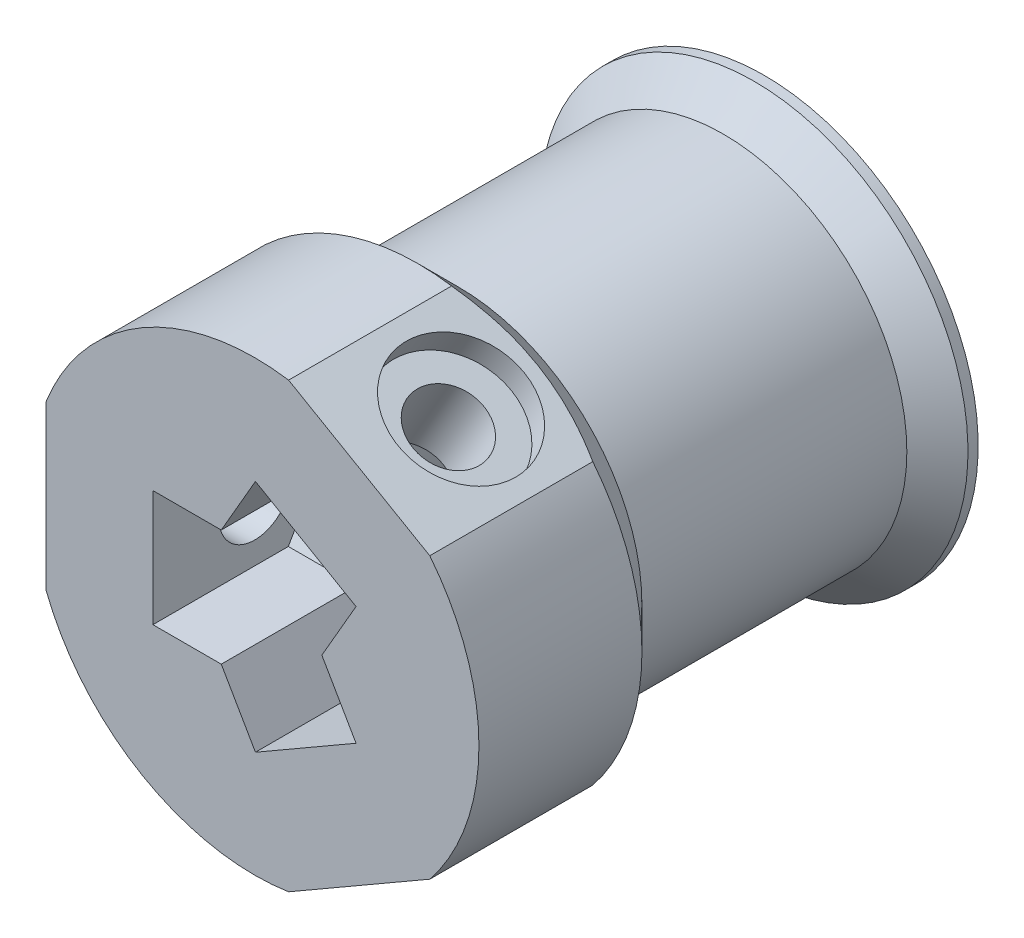
SolidWorks part; units mm, degrees
ref_plane "Front" through (0, 0, 0) normal (0, 0, 1) x (1, 0, 0)
ref_plane "Top" through (0, 0, 0) normal (0, 1, 0) x (1, 0, 0)
ref_plane "Right" through (0, 0, 0) normal (1, 0, 0) x (0, 0, -1)
sketch "Sketch1" plane through (0, 0, 0) normal (0, 0, 1) x (1, 0, 0)
  circle A0 centre (0, 0) radius 11
  dimension "D1" = 22
extrude "Boss-Base Flange" add sketch "Sketch1" along normal blind 2 draft 45
sketch "Sketch2" plane through (0, 0, 2) normal (0, 0, 1) x (1, 0, 0)
  circle A0 centre (0, 0) radius 9 construction
  circle A1 centre (0, 0) radius 9
extrude "Boss-Spectra Spool" add sketch "Sketch2" along normal blind 13
sketch "Sketch3" plane through (0, 0, 15) normal (0, 0, 1) x (1, 0, 0)
  circle A0 centre (0, 0) radius 9 construction
  circle A1 centre (0, 0) radius 9
extrude "Boss-Top Flange" add sketch "Sketch3" along normal blind 2 draft 45 draft outward yes
sketch "Sketch4" plane through (0, 0, 17) normal (0, 0, 1) x (1, 0, 0)
  line L0 (-11, 9.8044) -> (-11, -8.8054) construction
  circle A0 centre (0, 0) radius 11 construction
  circle A1 centre (0, 0) radius 11
extrude "Boss-Top Extension" add sketch "Sketch4" along normal blind 8
sketch "Sketch5" plane through (0, 0, 0) normal (0, 0, -1) x (-1, 0, 0)
  circle A0 centre (0, 0) radius 2.6
  dimension "D1" = 5.2
extrude "Cut-Stepper Shaft" cut sketch "Sketch5" against normal through all
ref_plane "Plane1" through (-11, 0, 0) normal (1, 0, 0) x (0, 0, -1)
sketch "Sketch7" plane through (-11, 0, 0) normal (1, 0, 0) x (0, 0, -1)
  line L0 (-17, 11) -> (-17, -11) construction
  circle A0 centre (-20, 0) radius 1.75
  dimension "D1" = 3.5
  dimension "D2" = 3
extrude "Cut-Set Screw Hole" cut sketch "Sketch7" along normal up to surface (11 mm away) up to plane "Right"
sketch "Sketch8" plane through (-11, 0, 0) normal (1, 0, 0) x (0, 0, -1)
  circle A0 centre (-20, 0) radius 3.1
  dimension "D1" = 6.2
extrude "Cut-Screw Head Slot" cut sketch "Sketch8" along normal blind 2
sketch "Sketch6" plane through (0, 0, 25) normal (0, 0, 1) x (1, 0, 0)
  line L1 (-10.247, 4) -> (-11, 4)
  line L2 (-10.247, 4) -> (-10.247, -4)
  line L3 (-10.247, -4) -> (-11, -4)
  line L4 (-11, 4) -> (-11, -4)
  circle A0 centre (0, 0) radius 11 construction
  dimension "D1" = 8
extrude "Cut-Flaten" cut sketch "Sketch6" against normal up to surface (8 mm away) up to face at (9, 0, 15)
sketch "Sketch10" plane through (0, 0, 0) normal (-1, 0, 0) x (0, 0, 1)
  line L1 (23.2909, 0) -> (21.6454, 2.85)
  line L2 (21.6454, 2.85) -> (18.3546, 2.85)
  line L3 (18.3546, 2.85) -> (16.7091, 0)
  line L4 (16.7091, 0) -> (18.3546, -2.85)
  line L5 (18.3546, -2.85) -> (21.6454, -2.85)
  line L6 (21.6454, -2.85) -> (23.2909, 0)
  circle A0 centre (20, 0) radius 2.85 construction
  dimension "D1" = 5.7
extrude "Cut-Nut Hole" cut sketch "Sketch10" along normal blind 5
sketch "Sketch11" plane through (0, 0, 0) normal (-1, 0, 0) x (0, 0, 1)
  line L0 (25, -11) -> (25, 11) construction
  line L1 (25, 2.85) -> (21.6454, 2.85)
  line L2 (25, 2.85) -> (25, -2.85)
  line L3 (25, -2.85) -> (21.6454, -2.85)
  line L4 (21.6454, 2.85) -> (21.6454, -2.85)
extrude "Cut-Nut Slot" cut sketch "Sketch11" along normal up to surface (5 mm away) up to face at (-5, 0, 21.75)
ref_axis "Axis1" through (0, 0, -80.9) along (0, 0, 1)
pattern_circular "CirPattern1" count 3 over 360 about axis through (0, 0, -80.9) along (0, 0, 1) of "Cut-Set Screw Hole", "Cut-Screw Head Slot", "Cut-Flaten", "Cut-Nut Hole", "Cut-Nut Slot"
sketch "Sketch13" plane through (0, 0, 25) normal (0, 0, 1) x (1, 0, 0)
  line L0 (-2.6, 0) -> (-5, 0) construction
  line L1 (-4.066, 1) -> (-4.9321, 0.5)
  line L2 (-4.9321, 0.5) -> (-4.9321, -0.5)
  line L3 (-4.9321, -0.5) -> (-4.066, -1)
  line L4 (-4.066, -1) -> (-3.2, -0.5)
  line L5 (-3.2, -0.5) -> (-3.2, 0.5)
  line L6 (-3.2, 0.5) -> (-4.066, 1)
  line L8 (-2.6, 2.85) -> (-2.6, -2.85) construction
  line L9 (-1.6454, 2.85) -> (-5, 2.85) construction
  line L10 (-1.6454, -2.85) -> (-5, -2.85) construction
  circle A0 centre (-4.066, 0) radius 0.866 construction
  arc A1 (-2.6, 0) -> (-1.3, -2.2517) centre (0, 0) ccw construction
  dimension "D1" = 2
  dimension "D2" = 0.6
extrude "Cut-Thread Hole" cut sketch "Sketch13" against normal through all
sketch "Sketch14" plane through (0, 0, 0) normal (0, 0, 1) x (1, 0, 0)
  line L0 (-11, 9.2906) -> (-11, -9.0052) construction
  circle A0 centre (0, 0) radius 11 construction
ref_plane "Plane2" through (-5.5, 0, 5.5) normal (-0.7071, 0, 0.7071) x (0.7071, 0, 0.7071)
sketch "Sketch15" plane through (-5.5, 0, 5.5) normal (-0.7071, 0, 0.7071) x (0.7071, 0, 0.7071)
  line L1 (-4.9399, 0.5) -> (-3.4399, 0.5)
  line L2 (-4.9399, 0.5) -> (-4.9399, -0.5)
  line L3 (-4.9399, -0.5) -> (-3.4399, -0.5)
  line L4 (-3.4399, 0.5) -> (-3.4399, -0.5)
  ellipse E0 centre (1.4142, 0) end of major axis (1.4142, -9) minor radius 6.364 construction
  point P10 (-3.4399, 0)
  dimension "D1" = 1
  dimension "D2" = 1.5
extrude "Cut-Extrude8" cut sketch "Sketch15" against normal through all and the other way through all
chamfer "Chamfer1" distance 1 angle 45 1 edges at (-4.9321, 0, 0.0673) first distance on face at (-6.9626, 0, 2.0978)
ref_plane "Plane3" through (0, 0, 8.5) normal (0, 0, 1) x (1, 0, 0)
mirror "Mirror1" about plane through (0, 0, 8.5) normal (0, 0, 1) of "Cut-Extrude8"
chamfer "Chamfer3" distance 0.3 angle 60 1 edges at (-2.6, 0, 0) first distance on face at (-4.796, 0, 0)
sketch "Sketch16" plane through (0, 0, 0) normal (0, 0, -1) x (-1, 0, 0)
  circle A0 centre (0, 0) radius 10.5
  circle A1 centre (0, 0) radius 11 construction
  dimension "D1" = 0.5
extrude "Cut-Truncate Base" cut sketch "Sketch16" against normal blind 5 flip side to cut
extrude "Cut-Extrude9" cut sketch "Sketch8<2>" along normal offset from surface (3 mm away) 1 up to face at (-9, 0, 18.25) offset beyond the face yes
sketch "Sketch8<2>" plane through (-11, 0, 0) normal (1, 0, 0) x (0, 0, -1) same geometry as "Sketch8"
